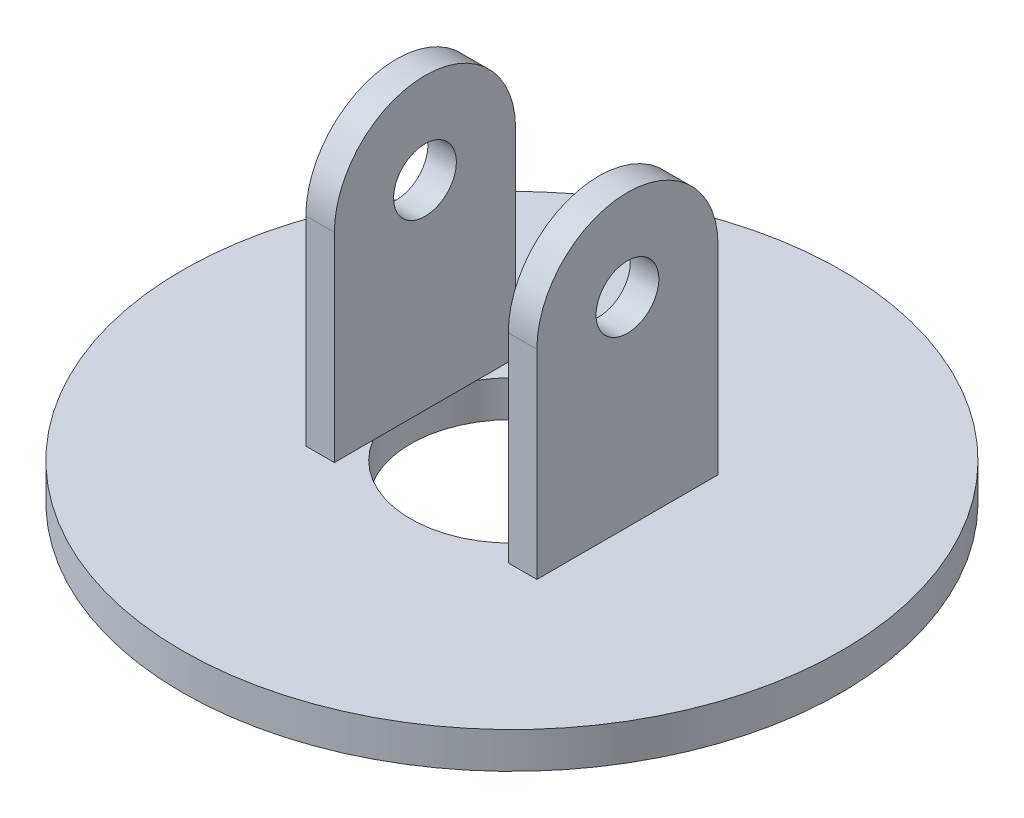
SolidWorks part; units mm, degrees
material "Cast Alloy Steel"
ref_plane "Front Plane" through (0, 0, 0) normal (0, 0, 1) x (1, 0, 0)
ref_plane "Top Plane" through (0, 0, 0) normal (0, 1, 0) x (1, 0, 0)
ref_plane "Right Plane" through (0, 0, 0) normal (1, 0, 0) x (0, 0, -1)
sketch "Sketch1" plane through (0, 0, 0) normal (0, 1, 0) x (1, 0, 0)
  circle A0 centre (0, 0) radius 115.5
  circle A1 centre (0, 0) radius 35.5
  dimension "D1" = 231
  dimension "D2" = 71
extrude "Boss-Extrude1" add sketch "Sketch1" along normal blind 12.7
sketch "Sketch2" plane through (0, 12.7, 0) normal (0, 1, 0) x (1, 0, 0)
  line L0 (0, 0) -> (115.5, 0) construction
  line L1 (115.5, 0) -> (40.48, 0) construction
  line L2 (40.48, 0) -> (35.48, 0) construction
  line L3 (0, -53.8202) -> (0, 51.6827) construction
  line L4 (40.48, -31.75) -> (30.48, -31.75)
  line L5 (40.48, -31.75) -> (40.48, 31.75)
  line L6 (40.48, 31.75) -> (30.48, 31.75)
  line L7 (30.48, -31.75) -> (30.48, 31.75)
  line L8 (40.48, -31.75) -> (30.48, 31.75) construction
  line L9 (40.48, 31.75) -> (30.48, -31.75) construction
  line L10 (-40.48, -31.75) -> (-30.48, -31.75)
  line L11 (-40.48, -31.75) -> (-40.48, 31.75)
  line L12 (-40.48, 31.75) -> (-30.48, 31.75)
  line L13 (-30.48, -31.75) -> (-30.48, 31.75)
  circle A0 centre (0, 0) radius 115.5 construction
  dimension "D1" = 75.02
  dimension "D2" = 5
  dimension "D3" = 10
  dimension "D4" = 63.5
extrude "Boss-Extrude2" add sketch "Sketch2" along normal blind 101.6
fillet "Fillet1" 2 edges at (35.48, 114.3, 31.75) (35.48, 114.3, -31.75) type full round first side face at (35.48, 63.5, 31.75) second side face at (35.48, 63.5, -31.75) middle face at (35.48, 114.3, 0)
ref_plane "Plane1" through (0, 0, 0) normal (-1, 0, 0) x (0, 0, 1)
fillet "Fillet2" 2 edges at (-35.48, 114.3, -31.75) (-35.48, 114.3, 31.75) type full round first side face at (-35.48, 63.5, -31.75) second side face at (-35.48, 63.5, 31.75) middle face at (-35.48, 114.3, 0)
sketch "Sketch3" plane through (-40.48, 0, 0) normal (-1, 0, 0) x (0, 0, 1)
  circle A0 centre (0, 82.55) radius 11
  dimension "D1" = 22
extrude "Cut-Extrude1" cut sketch "Sketch3" against normal blind 101.6
